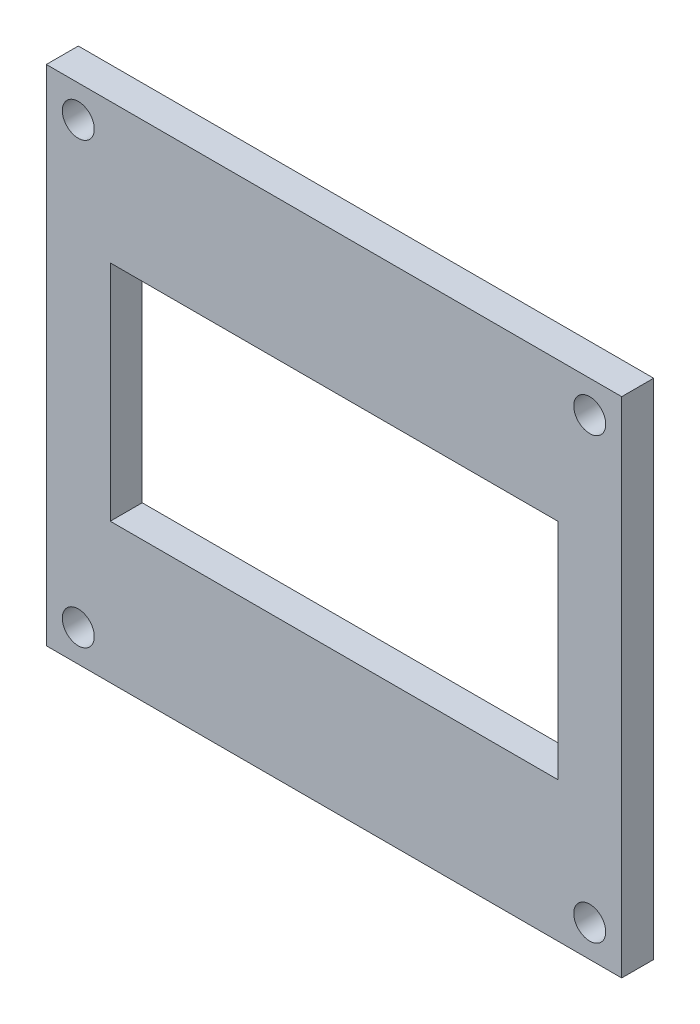
SolidWorks part; units mm, degrees
ref_plane "Front Plane" through (0, 0, 0) normal (0, 0, 1) x (1, 0, 0)
ref_plane "Top Plane" through (0, 0, 0) normal (0, 1, 0) x (1, 0, 0)
ref_plane "Right Plane" through (0, 0, 0) normal (1, 0, 0) x (0, 0, -1)
sketch "Sketch1" plane through (0, 0, 0) normal (0, 0, 1) x (1, 0, 0)
  line L1 (-28.575, -25.0031) -> (28.575, -25.0031)
  line L2 (-28.575, -25.0031) -> (-28.575, 25.0031)
  line L3 (-28.575, 25.0031) -> (28.575, 25.0031)
  line L4 (28.575, -25.0031) -> (28.575, 25.0031)
  line L5 (-28.575, -25.0031) -> (28.575, 25.0031) construction
  line L6 (-28.575, 25.0031) -> (28.575, -25.0031) construction
  line L7 (22.225, -11.1125) -> (-22.225, -11.1125)
  line L8 (22.225, -11.1125) -> (22.225, 11.1125)
  line L9 (22.225, 11.1125) -> (-22.225, 11.1125)
  line L10 (-22.225, -11.1125) -> (-22.225, 11.1125)
  line L11 (22.225, -11.1125) -> (-22.225, 11.1125) construction
  line L12 (22.225, 11.1125) -> (-22.225, -11.1125) construction
  point P0 (0, 0)
  point P6 (0, 0)
  dimension "D1" = 57.15
  dimension "D2" = 50.0062
  dimension "D3" = 22.225
  dimension "D4" = 44.45
extrude "Boss-Extrude1" add sketch "Sketch1" along normal blind 3.175
sketch "Sketch2" plane through (0, 0, 0) normal (0, 0, -1) x (-1, 0, 0)
  line L4 (-25.4, 21.8281) -> (25.4, 21.8281) construction
  line L5 (25.4, 21.8281) -> (25.4, -21.8281) construction
  line L6 (25.4, -21.8281) -> (-25.4, -21.8281) construction
  line L7 (-25.4, -21.8281) -> (-25.4, 21.8281) construction
  line L8 (-28.575, -25.0031) -> (-28.575, 25.0031) construction
  line L9 (28.575, 25.0031) -> (28.575, -25.0031) construction
  line L10 (-28.575, 25.0031) -> (28.575, 25.0031) construction
  line L11 (28.575, -25.0031) -> (-28.575, -25.0031) construction
  circle A0 centre (-25.4, -21.8281) radius 1.5875
  circle A1 centre (-25.4, 21.8281) radius 1.5875
  circle A2 centre (25.4, 21.8281) radius 1.5875
  circle A3 centre (25.4, -21.8281) radius 1.5875
  dimension "D5" = 3.175
  dimension "D1" = 3.175
  dimension "D2" = 3.175
  dimension "D3" = 3.175
  dimension "D4" = 3.175
extrude "Cut-Extrude1" cut sketch "Sketch2" against normal blind 3.175
